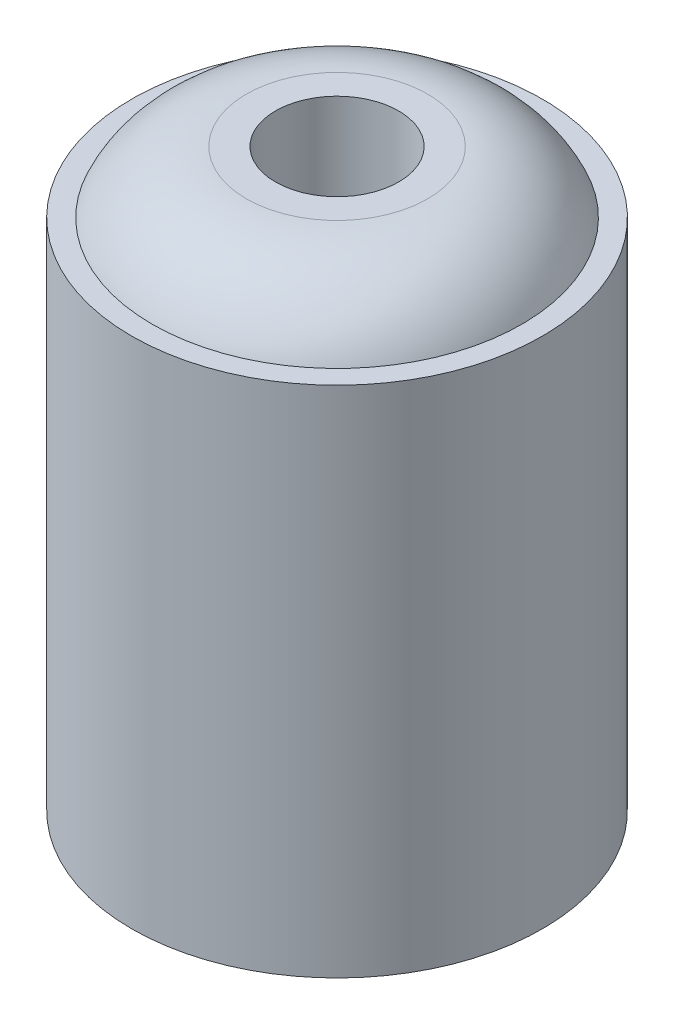
SolidWorks part; units mm, degrees
ref_plane "Front Plane" through (0, 0, 0) normal (0, 0, 1) x (1, 0, 0)
ref_plane "Top Plane" through (0, 0, 0) normal (0, 1, 0) x (1, 0, 0)
ref_plane "Right Plane" through (0, 0, 0) normal (1, 0, 0) x (0, 0, -1)
sketch "Sketch1" plane through (0, 0, 0) normal (0, 1, 0) x (1, 0, 0)
  circle A0 centre (0, 0) radius 10
  dimension "D1" = 20
extrude "Boss-Extrude2" add sketch "Sketch1" along normal blind 25
sketch "Sketch2" plane through (0, 0, 0) normal (0, 1, 0) x (1, 0, 0)
  circle A0 centre (0, 0) radius 9
  dimension "D1" = 18
extrude "Boss-Extrude3" add sketch "Sketch2" along normal blind 28
sketch "Sketch3" plane through (0, 0, 0) normal (0, 1, 0) x (1, 0, 0)
  circle A0 centre (0, 0) radius 3
  dimension "D1" = 6
extrude "Cut-Extrude1" cut sketch "Sketch3" along normal blind 42
fillet "Fillet2" radius 5 1 edges at (0, 28, 9)
